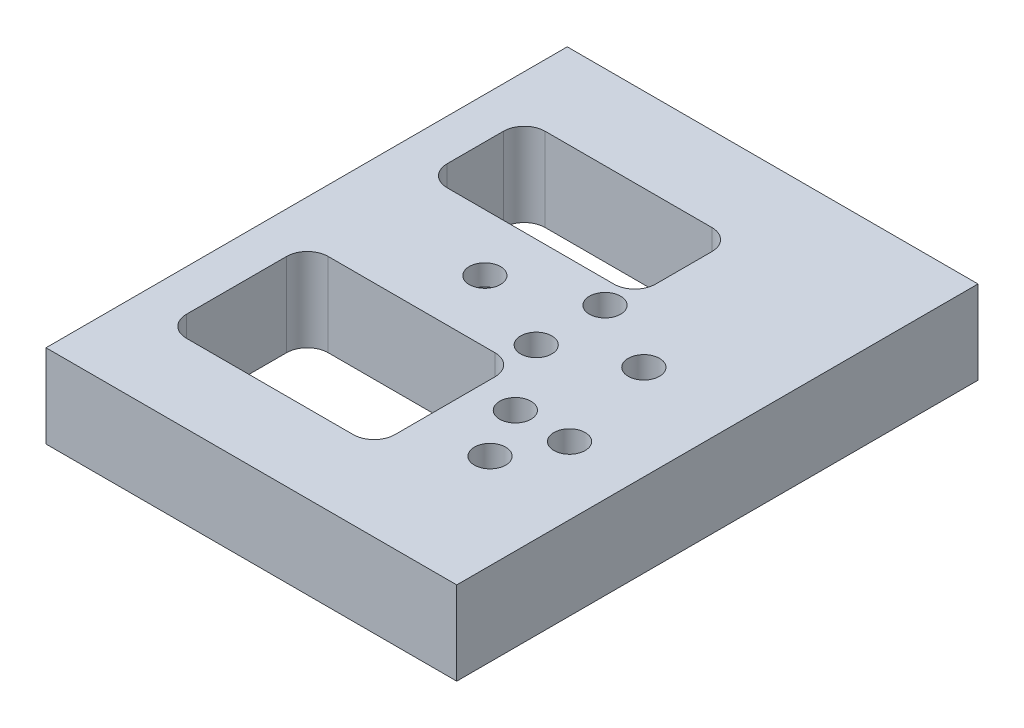
SolidWorks part; units mm, degrees
material "K110"
ref_plane "Front Plane" through (0, 0, 0) normal (0, 0, 1) x (1, 0, 0)
ref_plane "Top Plane" through (0, 0, 0) normal (0, 1, 0) x (1, 0, 0)
ref_plane "Right Plane" through (0, 0, 0) normal (1, 0, 0) x (0, 0, -1)
sketch "Sketch1" plane through (0, 0, 0) normal (0, 1, 0) x (1, 0, 0)
  line L1 (-98.5, -125) -> (98.5, -125)
  line L2 (-98.5, -125) -> (-98.5, 125)
  line L3 (-98.5, 125) -> (98.5, 125)
  line L4 (98.5, -125) -> (98.5, 125)
  line L5 (-98.5, -125) -> (98.5, 125) construction
  line L6 (-98.5, 125) -> (98.5, -125) construction
  point P0 (0, 0)
  dimension "D1" = 250
  dimension "D2" = 197
extrude "Boss-Extrude1" add sketch "Sketch1" against normal blind 40
sketch "Sketch2" plane through (0, 0, 0) normal (0, 1, 0) x (1, 0, 0)
  line L0 (-29.25, -63.53) -> (-29.25, -47.4) construction
  line L1 (-32.25, -44.4) -> (-36.25, -44.4) construction
  line L2 (-42.25, -38.4) -> (-42.25, -32.27) construction
  line L3 (-42.25, -32.27) -> (-61.37, -32.27) construction
  line L12 (-64.37, -35.27) -> (-64.37, -71.53) construction
  line L13 (-61.37, -74.53) -> (3.88, -74.53) construction
  line L14 (-17.25, -47.4) -> (-17.25, -63.53) construction
  line L15 (-10.25, -44.4) -> (-14.25, -44.4) construction
  line L16 (-4.25, -32.27) -> (-4.25, -38.4) construction
  line L17 (3.88, -32.27) -> (-4.25, -32.27) construction
  line L18 (6.88, -71.53) -> (6.88, -35.27) construction
  line L19 (-29.25, -63.53) -> (-29.25, -47.4)
  line L20 (-32.25, -44.4) -> (-36.25, -44.4)
  line L21 (-42.25, -38.4) -> (-42.25, -32.27)
  line L22 (-42.25, -32.27) -> (-61.37, -32.27)
  line L23 (-64.37, -35.27) -> (-64.37, -71.53)
  line L24 (-61.37, -74.53) -> (3.88, -74.53)
  line L25 (-17.25, -47.4) -> (-17.25, -63.53)
  line L26 (-10.25, -44.4) -> (-14.25, -44.4)
  line L27 (-4.25, -32.27) -> (-4.25, -38.4)
  line L28 (3.88, -32.27) -> (-4.25, -32.27)
  line L29 (6.88, -71.53) -> (6.88, -35.27)
  line L30 (-4.25, 47.73) -> (3.88, 47.73) construction
  line L31 (-4.25, 69.53) -> (-4.25, 47.73) construction
  line L32 (-42.25, 69.53) -> (-4.25, 69.53) construction
  line L33 (-42.25, 47.73) -> (-42.25, 69.53) construction
  line L34 (-61.37, 47.73) -> (-42.25, 47.73) construction
  line L35 (-64.37, 71.53) -> (-64.37, 50.73) construction
  line L36 (3.88, 74.53) -> (-61.37, 74.53) construction
  line L37 (6.88, 50.73) -> (6.88, 71.53) construction
  line L38 (-4.25, 47.73) -> (3.88, 47.73)
  line L39 (-4.25, 69.53) -> (-4.25, 47.73)
  line L40 (-42.25, 69.53) -> (-4.25, 69.53)
  line L41 (-42.25, 47.73) -> (-42.25, 69.53)
  line L42 (-61.37, 47.73) -> (-42.25, 47.73)
  line L43 (-64.37, 71.53) -> (-64.37, 50.73)
  line L44 (3.88, 74.53) -> (-61.37, 74.53)
  line L45 (6.88, 50.73) -> (6.88, 71.53)
  arc A0 (-29.25, -47.4) -> (-32.25, -44.4) centre (-32.25, -47.4) ccw construction
  arc A1 (-42.25, -38.4) -> (-36.25, -44.4) centre (-36.25, -38.4) ccw construction
  arc A2 (-61.37, -32.27) -> (-64.37, -35.27) centre (-61.37, -35.27) ccw construction
  arc A3 (-64.37, -71.53) -> (-61.37, -74.53) centre (-61.37, -71.53) ccw construction
  arc A4 (3.88, -74.53) -> (6.88, -71.53) centre (3.88, -71.53) ccw construction
  arc A5 (-29.25, -63.53) -> (-17.25, -63.53) centre (-23.25, -63.53) ccw construction
  arc A6 (-14.25, -44.4) -> (-17.25, -47.4) centre (-14.25, -47.4) ccw construction
  arc A7 (-10.25, -44.4) -> (-4.25, -38.4) centre (-10.25, -38.4) ccw construction
  arc A8 (6.88, -35.27) -> (3.88, -32.27) centre (3.88, -35.27) ccw construction
  arc A9 (-29.25, -47.4) -> (-32.25, -44.4) centre (-32.25, -47.4) ccw
  arc A10 (-42.25, -38.4) -> (-36.25, -44.4) centre (-36.25, -38.4) ccw
  arc A11 (-61.37, -32.27) -> (-64.37, -35.27) centre (-61.37, -35.27) ccw
  arc A12 (-64.37, -71.53) -> (-61.37, -74.53) centre (-61.37, -71.53) ccw
  arc A13 (3.88, -74.53) -> (6.88, -71.53) centre (3.88, -71.53) ccw
  arc A14 (-29.25, -63.53) -> (-17.25, -63.53) centre (-23.25, -63.53) ccw
  arc A15 (-14.25, -44.4) -> (-17.25, -47.4) centre (-14.25, -47.4) ccw
  arc A16 (-10.25, -44.4) -> (-4.25, -38.4) centre (-10.25, -38.4) ccw
  arc A17 (6.88, -35.27) -> (3.88, -32.27) centre (3.88, -35.27) ccw
  circle A18 centre (53, -63.53) radius 2.5 construction
  circle A19 centre (66, -38.4) radius 2.5 construction
  circle A20 centre (40, -38.4) radius 2.5 construction
  circle A21 centre (17.88, -6.27) radius 2.5 construction
  circle A22 centre (17.88, 26.73) radius 2.5 construction
  arc A23 (3.88, 47.73) -> (6.88, 50.73) centre (3.88, 50.73) ccw construction
  arc A24 (-64.37, 50.73) -> (-61.37, 47.73) centre (-61.37, 50.73) ccw construction
  arc A25 (-61.37, 74.53) -> (-64.37, 71.53) centre (-61.37, 71.53) ccw construction
  arc A26 (6.88, 71.53) -> (3.88, 74.53) centre (3.88, 71.53) ccw construction
  circle A27 centre (53, -63.53) radius 2.5
  circle A28 centre (66, -38.4) radius 2.5
  circle A29 centre (40, -38.4) radius 2.5
  circle A30 centre (17.88, -6.27) radius 2.5
  circle A31 centre (17.88, 26.73) radius 2.5
  arc A32 (3.88, 47.73) -> (6.88, 50.73) centre (3.88, 50.73) ccw
  arc A33 (-64.37, 50.73) -> (-61.37, 47.73) centre (-61.37, 50.73) ccw
  arc A34 (-61.37, 74.53) -> (-64.37, 71.53) centre (-61.37, 71.53) ccw
  arc A35 (6.88, 71.53) -> (3.88, 74.53) centre (3.88, 71.53) ccw
sketch "Sketch3" plane through (0, 0, 0) normal (0, 1, 0) x (1, 0, 0)
  line L1 (-68.745, 84.63) -> (11.255, 84.63)
  line L2 (-78.745, 74.63) -> (-78.745, 47.63)
  line L3 (-68.745, 37.63) -> (11.255, 37.63)
  line L4 (21.255, 74.63) -> (21.255, 47.63)
  line L8 (-64.37, -53.4) -> (6.88, -53.4) construction
  line L9 (-68.745, -19.4) -> (11.255, -19.4)
  line L10 (-78.745, -29.4) -> (-78.745, -77.4)
  line L11 (-68.745, -87.4) -> (11.255, -87.4)
  line L12 (21.255, -29.4) -> (21.255, -77.4)
  line L13 (-64.37, -35.27) -> (-64.37, -71.53) construction
  line L14 (6.88, -71.53) -> (6.88, -35.27) construction
  line L15 (-28.745, -74.53) -> (-28.745, -19.4) construction
  line L16 (-61.37, -74.53) -> (3.88, -74.53) construction
  line L17 (-28.745, 84.63) -> (-28.745, 47.73) construction
  line L18 (-64.37, 61.13) -> (6.88, 61.13) construction
  line L19 (-64.37, 71.53) -> (-64.37, 50.73) construction
  line L20 (6.88, 50.73) -> (6.88, 71.53) construction
  arc A0 (-78.745, 47.63) -> (-68.745, 37.63) centre (-68.745, 47.63) ccw
  arc A1 (11.255, 37.63) -> (21.255, 47.63) centre (11.255, 47.63) ccw
  arc A2 (21.255, 74.63) -> (11.255, 84.63) centre (11.255, 74.63) ccw
  arc A3 (-68.745, 84.63) -> (-78.745, 74.63) centre (-68.745, 74.63) ccw
  circle A4 centre (17.88, 26.73) radius 7.5
  circle A5 centre (17.88, -6.27) radius 7.5
  circle A6 centre (53, -63.53) radius 7.5
  circle A7 centre (66, -38.4) radius 7.5
  circle A8 centre (40, -38.4) radius 7.5
  arc A9 (-78.745, -77.4) -> (-68.745, -87.4) centre (-68.745, -77.4) ccw
  arc A10 (11.255, -87.4) -> (21.255, -77.4) centre (11.255, -77.4) ccw
  arc A11 (21.255, -29.4) -> (11.255, -19.4) centre (11.255, -29.4) ccw
  arc A12 (-68.745, -19.4) -> (-78.745, -29.4) centre (-68.745, -29.4) ccw
  dimension "D5" = 10
  dimension "D6" = 15
  dimension "D11" = 10
  dimension "D2" = 100
  dimension "D3" = 47
  dimension "D7" = 68
  dimension "D8" = 100
extrude "Cut-Extrude2" cut sketch "Sketch3" against normal up to next
sketch "Sketch4" plane through (0, -40, 0) normal (0, -1, 0) x (1, 0, 0)
  circle A0 centre (17.88, -26.73) radius 9
  circle A1 centre (17.88, 6.27) radius 9
  circle A2 centre (40, 38.4) radius 9
  circle A3 centre (66, 38.4) radius 9
  circle A4 centre (53, 63.53) radius 9
  dimension "D1" = 18
extrude "Cut-Extrude3" cut sketch "Sketch4" against normal blind 5
extrude "Cut-Extrude9" cut sketch "Sketch11" against normal through all
sketch "Sketch11" plane through (88.13, 0, 0) normal (0, 1, 0) x (1, 0, 0)
  circle A0 centre (-35.13, 10.23) radius 7.5
  circle A1 centre (-111.38, 10.23) radius 7.5
extrude "Cut-Extrude10" cut sketch "Sketch12" against normal blind 5
sketch "Sketch12" plane through (88.13, -40, 0) normal (0, -1, 0) x (1, 0, 0)
  circle A0 centre (-35.13, -10.23) radius 10
extrude "Cut-Extrude11" cut sketch "Sketch13" against normal blind 30
sketch "Sketch13" plane through (88.13, -40, 0) normal (0, -1, 0) x (1, 0, 0)
  circle A0 centre (-111.38, -10.23) radius 10
